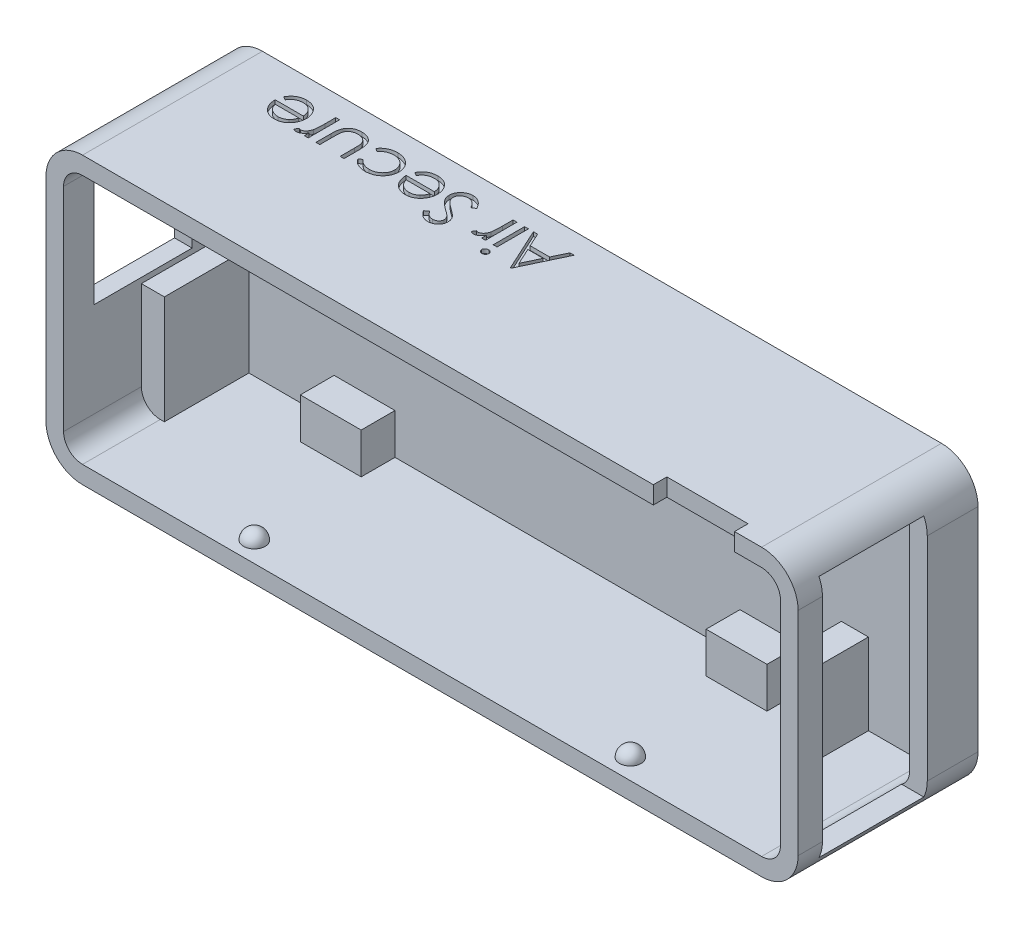
SolidWorks part; units mm, degrees
material "PLA"
ref_plane "Front Plane" through (0, 0, 0) normal (0, 0, 1) x (1, 0, 0)
ref_plane "Top Plane" through (0, 0, 0) normal (0, 1, 0) x (1, 0, 0)
ref_plane "Right Plane" through (0, 0, 0) normal (1, 0, 0) x (0, 0, -1)
sketch "Sketch2" plane through (0, 0, 0) normal (0, 0, 1) x (1, 0, 0)
  line L1 (2.4, -43.153) -> (-47.8, -43.153)
  line L2 (3.8, -44.553) -> (3.8, -60.253)
  line L3 (2.4, -61.653) -> (-47.8, -61.653)
  line L4 (-49.2, -44.553) -> (-49.2, -60.253)
  arc A0 (3.8, -44.553) -> (2.4, -43.153) centre (2.4, -44.553) ccw
  arc A1 (2.4, -61.653) -> (3.8, -60.253) centre (2.4, -60.253) ccw
  arc A2 (-49.2, -60.253) -> (-47.8, -61.653) centre (-47.8, -60.253) ccw
  arc A3 (-49.2, -44.553) -> (-47.8, -43.153) centre (-47.8, -44.553) cw
  point P2 (3.8, -43.153)
  point P9 (-49.2, -61.653)
  point P14 (-49.2, -43.153)
  dimension "D1" = 18.5
  dimension "D3" = 1.4
  dimension "D2" = 53
extrude "Boss-Extrude1" add sketch "Sketch2" along normal blind 12 contours L2 A1 L3 A2 L4 A3 L1 A0
shell "Shell1" thickness 1.3 removed face at (-22.7, -52.403, 12) outward yes
sketch "Sketch3" plane through (0, -61.653, 0) normal (0, 1, 0) x (1, 0, 0)
  line L0 (-9.6, -10.5) -> (-8, -10.5)
  line L1 (2.4, -12) -> (-47.8, -12) construction
  line L2 (5.1, -12) -> (5.1, 1.3) construction
  arc A0 (-8, -10.5) -> (-9.6, -10.5) centre (-8.8, -10.5) ccw
  dimension "D4" = 0.8
  dimension "D1" = 1.5
  dimension "D2" = 13.9
  dimension "D3" = 1.6
revolve "Revolve1" add sketch "Sketch3" angle 360 about L0
ref_plane "Plane1" through (0, -52.403, 0) normal (0, 1, 0) x (1, 0, 0)
mirror "Mirror1" about plane through (0, -52.403, 0) normal (0, 1, 0) of "Revolve1"
sketch "Sketch9" plane through (0, 0, 0) normal (0, 0, 1) x (1, 0, 0)
  line L0 (-47.5, -61.653) -> (-47.5, -53.653)
  line L1 (2.4, -61.653) -> (-47.8, -61.653) construction
  line L2 (2.4, -43.153) -> (-47.8, -43.153) construction
  line L3 (-49.2, -44.553) -> (-49.2, -60.253) construction
  line L4 (-47.5, -53.653) -> (-49.2, -53.653)
  line L8 (2.4, -43.153) -> (-47.8, -43.153)
  line L9 (-49.2, -44.553) -> (-49.2, -60.253)
  line L10 (-47.8, -61.653) -> (2.4, -61.653)
  line L11 (3.8, -60.253) -> (3.8, -44.553)
  line L12 (-47.2, -43.153) -> (-47.8, -43.153)
  line L13 (-49.2, -44.553) -> (-49.2, -60.253)
  line L14 (-47.8, -61.653) -> (-47.5, -61.653)
  arc A4 (3.8, -44.553) -> (2.4, -43.153) centre (2.4, -44.553) ccw
  arc A5 (-47.8, -43.153) -> (-49.2, -44.553) centre (-47.8, -44.553) ccw
  arc A6 (-49.2, -60.253) -> (-47.8, -61.653) centre (-47.8, -60.253) ccw
  arc A7 (2.4, -61.653) -> (3.8, -60.253) centre (2.4, -60.253) ccw
  arc A9 (-47.8, -43.153) -> (-49.2, -44.553) centre (-47.8, -44.553) ccw
  arc A10 (-49.2, -60.253) -> (-47.8, -61.653) centre (-47.8, -60.253) ccw
  line M4 (-49.2, -44.553) -> (-49.2, -60.253)
  arc M5 (-49.2, -60.253) -> (-47.8, -61.653) centre (-47.8, -60.253) ccw
  line M6 (-47.8, -61.653) -> (2.4, -61.653)
  dimension "D1" = 1.7
  dimension "D3" = 8
  dimension "D2" = 0
extrude "Boss-Extrude3" add sketch "Sketch9" along normal blind 6.25 contours L0 L4 M4 M5 M6 region at (-48.3329, -57.5354, 0)
sketch "Sketch10" plane through (5.1, 0, 0) normal (1, 0, 0) x (0, 0, -1)
  line L0 (6.6, -52.403) -> (-6.6, -52.403) construction
  line L1 (-2.45, -61.403) -> (-10.2, -61.403)
  line L2 (-2.45, -61.403) -> (-2.45, -43.403)
  line L3 (-2.45, -43.403) -> (-10.2, -43.403)
  line L4 (-10.2, -61.403) -> (-10.2, -43.403)
  line L5 (-2.45, -61.403) -> (-10.2, -43.403) construction
  line L6 (-2.45, -43.403) -> (-10.2, -61.403) construction
  line L7 (1.3, -44.553) -> (1.3, -60.253) construction
  point P0 (-6.325, -52.403)
  dimension "D1" = 0
  dimension "D2" = 3.75
  dimension "D3" = 18
  dimension "D4" = 7.75
extrude "Cut-Extrude1" cut sketch "Sketch10" against normal blind 2.7
sketch "Sketch11" plane through (0, 0, 0) normal (0, 0, 1) x (1, 0, 0)
  line L0 (6.6, -52.403) -> (-6.6, -52.403) construction
  line L1 (-1.7, -61.653) -> (-3.7, -61.653)
  line L2 (-1.7, -61.653) -> (-1.7, -55.653)
  line L3 (-1.7, -43.153) -> (-3.7, -43.153)
  line L4 (-3.7, -61.653) -> (-3.7, -55.653)
  line L5 (-1.7, -61.653) -> (-3.7, -43.153) construction
  line L6 (-1.7, -43.153) -> (-3.7, -61.653) construction
  line L7 (-1.7, -49.153) -> (-3.7, -49.153)
  line L8 (-50.5, -44.553) -> (-50.5, -60.253) construction
  line L9 (-1.7, -55.653) -> (-3.7, -55.653)
  line L10 (-1.7, -49.153) -> (-1.7, -43.153)
  line L11 (-3.7, -49.153) -> (-3.7, -43.153)
  point P0 (-2.7, -52.403)
  dimension "D1" = 0
  dimension "D2" = 47.8
  dimension "D3" = 2
  dimension "D4" = 18.5
  dimension "D5" = 6
  dimension "D6" = 6
extrude "Boss-Extrude4" add sketch "Sketch11" along normal blind 4
ref_plane "Plane2" through (-22.7, 0, 0) normal (-1, 0, 0) x (0, 0, 1)
mirror "Mirror3" about plane through (-22.7, 0, 0) normal (-1, 0, 0) of "Revolve1", "Mirror1"
sketch "Sketch12" plane through (0, 0, 0) normal (0, 0, 1) x (1, 0, 0)
  line L0 (-3.7, -61.653) -> (-47.5, -61.653) construction
  line L1 (-6.7, -61.653) -> (-11.2, -61.653)
  line L2 (-6.7, -61.653) -> (-6.7, -58.653)
  line L3 (-6.7, -58.653) -> (-11.2, -58.653)
  line L4 (-11.2, -61.653) -> (-11.2, -58.653)
  line L5 (-3.7, -55.653) -> (-3.7, -61.653) construction
  dimension "D1" = 3
  dimension "D2" = 4.5
  dimension "D3" = 3
extrude "Boss-Extrude5" add sketch "Sketch12" along normal blind 2.5
pattern_linear "LPattern1" count 2 spacing 30 along (-1, 0, 0) count 2 spacing 15.5 along (0, 1, 0) of "Boss-Extrude5"
sketch "Sketch19" plane through (0, -41.853, 0) normal (0, 1, 0) x (1, 0, 0)
  line L0 (-23.0553, -0.2364) -> (-45.0839, -0.2364) construction
  text T0 "Air Secure"
extrude "Cut-Extrude4" cut sketch "Sketch19" against normal blind 0.3
sketch "Sketch21" plane through (0, -62.953, 0) normal (0, -1, 0) x (1, 0, 0)
  line L0 (-45.043, 0.3023) -> (0, 0.3023) construction
  text T0 "Air Secure"
extrude "Cut-Extrude5" cut sketch "Sketch21" against normal blind 0.3
sketch "Sketch22" plane through (0, 0, -1.3) normal (0, 0, -1) x (-1, 0, 0)
  line L1 (3.7, -55.653) -> (3.7, -61.653) construction
  circle A0 centre (11.7, -51.9812) radius 1.75
  dimension "D2" = 3.5
  dimension "D1" = 8
extrude "Cut-Extrude6" [suppressed] cut sketch "Sketch22" against normal blind 1.3
pattern_linear "LPattern2" [suppressed] count 4 spacing 10 of bodies 114
sketch "Sketch23" plane through (-50.5, 0, 0) normal (-1, 0, 0) x (0, 0, 1)
  line L0 (12, -44.553) -> (12, -60.253) construction
  line L2 (12, -61.653) -> (6.25, -61.653) construction
  circle A0 centre (5.5, -52.403) radius 1.75
  dimension "D3" = 3.5
  dimension "D1" = 6.5
  dimension "D2" = 9.25
extrude "Cut-Extrude7" [suppressed] cut sketch "Sketch23" against normal blind 1.3
sketch "Sketch24" plane through (0, -41.853, 0) normal (0, 1, 0) x (1, 0, 0)
  line L0 (2.4, -12) -> (2.4, 1.3) construction
  line L1 (2.4, -12) -> (-47.8, -12) construction
  circle A0 centre (-7.6, -6) radius 1.25
  dimension "D1" = 2.5
  dimension "D2" = 10
  dimension "D3" = 6
extrude "Cut-Extrude8" [suppressed] cut sketch "Sketch24" against normal blind 1.3
pattern_linear "LPattern3" [suppressed] count 4 spacing 10 count 2 spacing 19.8 of bodies 117
sketch "Sketch25" plane through (0, -41.853, 0) normal (0, 1, 0) x (1, 0, 0)
  line L0 (2.4, -12) -> (-47.8, -12) construction
  line L1 (0.4, -12) -> (-5.6, -12)
  line L2 (0.4, -12) -> (0.4, -11)
  line L3 (0.4, -11) -> (-5.6, -11)
  line L4 (-5.6, -12) -> (-5.6, -11)
  line L5 (2.4, -12) -> (2.4, 1.3) construction
  dimension "D1" = 2
  dimension "D2" = 1
  dimension "D3" = 6
extrude "Cut-Extrude9" cut sketch "Sketch25" against normal blind 10
mirror "Mirror2" [suppressed] about plane through (0, -52.403, 0) normal (0, 1, 0)
sketch "Sketch26" plane through (-50.5, 0, 0) normal (-1, 0, 0) x (0, 0, 1)
  line L0 (-1.3, -44.553) -> (-1.3, -60.253) construction
  line L1 (9.75, -53.253) -> (2.5, -53.253)
  line L2 (9.75, -53.253) -> (9.75, -43.253)
  line L3 (9.75, -43.253) -> (2.5, -43.253)
  line L4 (2.5, -53.253) -> (2.5, -43.253)
  line L5 (12, -41.853) -> (-1.3, -41.853) construction
  dimension "D1" = 10
  dimension "D2" = 3.8
  dimension "D3" = 7.25
  dimension "D4" = 1.4
extrude "Cut-Extrude10" cut sketch "Sketch26" against normal blind 4
equation "\"D1@Boss-Extrude1\" = \"BoxDepth\"'depth"
equation "\"D1@Shell1\"=\"WallThickness\""
equation "\"BoxWidth\"= 18.5mm'inner width"
equation "\"D1@Sketch2\"=\"BoxWidth\""
equation "\"BoxLength\"= 53mm'inner length"
equation "\"D2@Sketch2\"=\"BoxLength\""
equation "\"D3@Sketch2\" = \"CornerRadius\"'inner corner radius"
equation "\"CornerRadius\"= 1.4mm'inner corner radius"
equation "\"BoxDepth\"= 12mm'inner depth"
equation "\"WallThickness\"= 1.3mm"
equation "\"LatchOffEdge\"= 1.5mm"
equation "\"LatchRadius\"= 0.8mm"
equation "\"D2@Sketch3\"=(\"BoxLength\"+\"WallThickness\"*2)/4"
equation "\"D1@Sketch3\"=\"LatchOffEdge\""
equation "\"D3@Sketch3\"=\"LatchRadius\"*2"
equation "\"D4@Sketch3\"=\"LatchRadius\""
equation "\"PortWidth\"= 18mm"
equation "\"PortHeight\"= 7.75mm"
equation "\"PortOffsetBottom\"= 3.75mm"
equation "\"D3@Sketch10\"=\"PortWidth\""
equation "\"D2@Sketch10\"=\"PortOffsetBottom\""
equation "\"D4@Sketch10\"=\"PortHeight\""
equation "\"D1@Cut-Extrude1\"=\"WallThickness\"+\"CornerRadius\""
equation "\"D4@Sketch11\"=\"BoxWidth\""
equation "\"D4@LPattern1\"=\"BoxWidth\"-\"D1@Sketch12\""
equation "\"D1@Cut-Extrude6\"=\"WallThickness\""
equation "\"D2@Sketch23\"=\"BoxWidth\"/2"
equation "\"D1@Cut-Extrude7\"=\"WallThickness\""
equation "\"D1@Cut-Extrude8\"=\"WallThickness\""
equation "\"D4@LPattern3\"=\"BoxWidth\"+\"WallThickness\""
